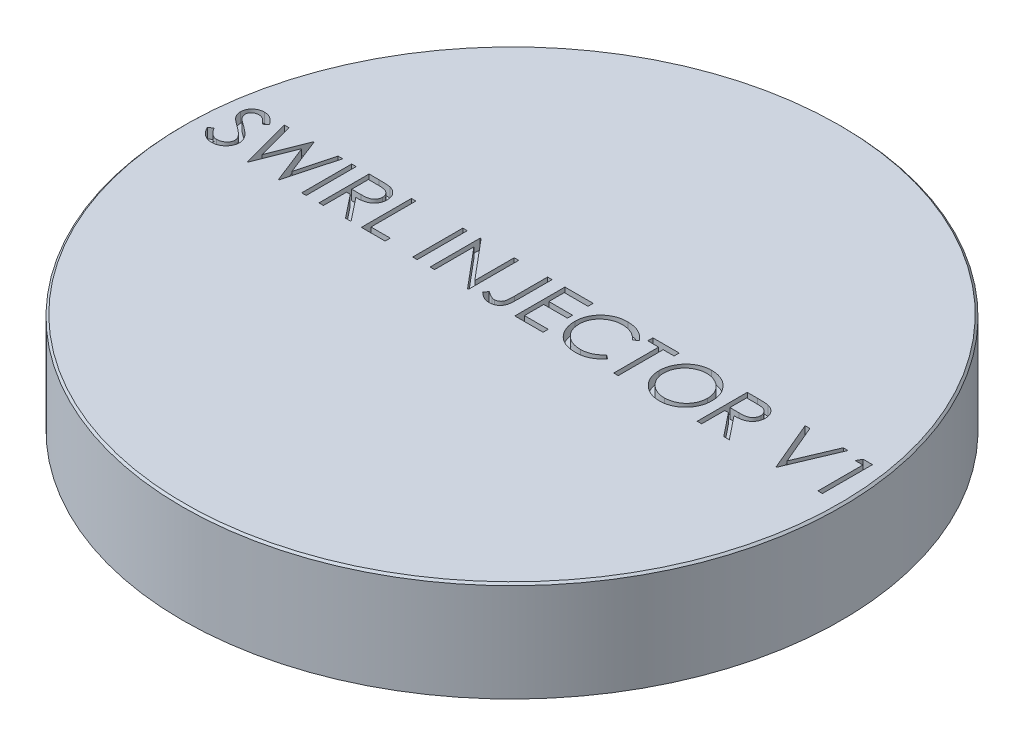
SolidWorks part; units mm, degrees
material "Brass"
ref_plane "Front Plane" through (0, 0, 0) normal (0, 0, 1) x (1, 0, 0)
ref_plane "Top Plane" through (0, 0, 0) normal (0, 1, 0) x (1, 0, 0)
ref_plane "Right Plane" through (0, 0, 0) normal (1, 0, 0) x (0, 0, -1)
sketch "Sketch3" plane through (0, 0, 0) normal (0, 1, 0) x (1, 0, 0)
  circle A0 centre (0, 0) radius 4.1783
  dimension "D1" = 8.3566
extrude "Boss-Extrude1" add sketch "Sketch3" along normal blind 1.27
chamfer "Chamfer1" distance 0.0254 angle 45 1 edges at (0, 1.27, 4.1783)
sketch "Sketch4" plane through (0, 1.27, 0) normal (0, 1, 0) x (1, 0, 0)
  line L0 (-4.0021, 0) -> (4.0021, 0) construction
  text T0 "SWIRL INJECTOR V1" font "Century Gothic" height 0.635
  point P4 (0, 0)
  point P6 (-3.7646, 0)
  point P7 (-4.0021, 0)
extrude "Cut-Extrude1" cut sketch "Sketch4" against normal blind 0.127
